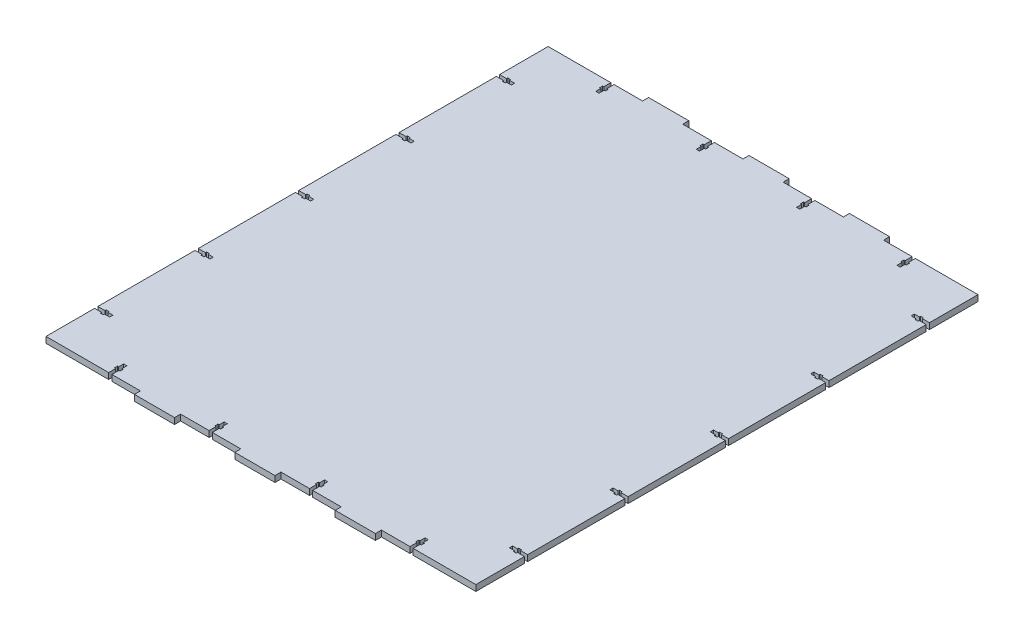
SolidWorks part; units mm, degrees
ref_plane "Front Plane" through (0, 0, 0) normal (0, 0, 1) x (1, 0, 0)
ref_plane "Top Plane" through (0, 0, 0) normal (0, 1, 0) x (1, 0, 0)
ref_plane "Right Plane" through (0, 0, 0) normal (1, 0, 0) x (0, 0, -1)
sketch "Sketch1" plane through (0, 0, 0) normal (0, 1, 0) x (1, 0, 0)
  line L1 (-214, -250) -> (214, -250)
  line L2 (-214, -250) -> (-214, 250)
  line L3 (-214, 250) -> (214, 250)
  line L4 (214, -250) -> (214, 250)
  line L5 (-214, -250) -> (214, 250) construction
  line L6 (-214, 250) -> (214, -250) construction
  point P0 (0, 0)
  dimension "D1" = 428
  dimension "D2" = 500
extrude "Boss-Extrude1" add sketch "Sketch1" along normal blind 6
sketch "Sketch2" plane through (0, 0, 0) normal (0, -1, 0) x (1, 0, 0)
  line L14 (0, 0) -> (0, 133.2527) construction
  line L15 (0, 0) -> (-145.1849, 0) construction
  line L40 (-148.4, 256) -> (-151.6, 256) construction
  line L41 (-148.4, 256) -> (-151.6, 256) construction
  line L42 (-48.4, 256) -> (-51.6, 256) construction
  line L43 (-48.4, 256) -> (-51.6, 256) construction
  line L44 (-148.4, 256) -> (-51.6, 256) construction
  line L45 (-214, 250) -> (214, 250) construction
  line L46 (-120, 256) -> (-80, 256)
  line L47 (-120, 256) -> (-120, 250)
  line L48 (-120, 250) -> (-80, 250)
  line L49 (-80, 256) -> (-80, 250)
  line L50 (-20, 250) -> (20, 250)
  line L51 (20, 256) -> (20, 250)
  line L52 (-20, 256) -> (20, 256)
  line L53 (-20, 256) -> (-20, 250)
  line L54 (80, 250) -> (120, 250)
  line L55 (120, 256) -> (120, 250)
  line L56 (80, 256) -> (120, 256)
  line L57 (80, 256) -> (80, 250)
  line L58 (120, -256) -> (120, -250)
  line L59 (80, -250) -> (120, -250)
  line L60 (80, -256) -> (120, -256)
  line L61 (80, -256) -> (80, -250)
  line L62 (20, -256) -> (20, -250)
  line L63 (-20, -256) -> (20, -256)
  line L64 (-20, -250) -> (20, -250)
  line L65 (-20, -256) -> (-20, -250)
  line L66 (-120, -250) -> (-80, -250)
  line L67 (-120, -256) -> (-120, -250)
  line L68 (-120, -256) -> (-80, -256)
  line L69 (-80, -256) -> (-80, -250)
  point P50 (-100, 256)
  dimension "D3" = 40
  dimension "D4" = 3
extrude "Boss-Extrude2" add sketch "Sketch2" against normal blind 6
sketch "Sketch3" plane through (0, 0, 0) normal (0, -1, 0) x (1, 0, 0)
  line L0 (-220, -198.4) -> (-220, -201.6) construction
  line L1 (-220, -198.4) -> (-220, -201.6)
  line L2 (-220, -200) -> (-193.4637, -200) construction
  line L3 (-214, -250) -> (-214, 250) construction
  line L4 (-199, -201.6) -> (-204, -201.6)
  line L5 (-199, -201.6) -> (-199, -198.4)
  line L6 (-199, -198.4) -> (-204, -198.4)
  line L7 (-214, -201.6) -> (-214, -198.4)
  line L8 (-199, -201.6) -> (-214, -198.4) construction
  line L9 (-199, -198.4) -> (-214, -201.6) construction
  line L10 (-207, -198.4) -> (-214, -198.4)
  line L11 (-204, -202.8) -> (-207, -202.8)
  line L12 (-204, -202.8) -> (-204, -201.6)
  line L13 (-204, -197.2) -> (-207, -197.2)
  line L14 (-207, -202.8) -> (-207, -201.6)
  line L15 (-204, -202.8) -> (-207, -197.2) construction
  line L16 (-204, -197.2) -> (-207, -202.8) construction
  line L17 (-207, -201.6) -> (-214, -201.6)
  line L18 (-199, -101.6) -> (-204, -101.6)
  line L19 (-207, -198.4) -> (-207, -197.2)
  line L20 (-204, -198.4) -> (-204, -197.2)
  line L21 (204, 202.8) -> (207, 197.2) construction
  line L22 (-199, -101.6) -> (-199, -98.4)
  line L24 (-199, -98.4) -> (-204, -98.4)
  line L25 (-214, -101.6) -> (-214, -98.4)
  line L26 (-207, -98.4) -> (-214, -98.4)
  line L27 (-204, -102.8) -> (-207, -102.8)
  line L28 (-204, -102.8) -> (-204, -101.6)
  line L29 (-204, -97.2) -> (-207, -97.2)
  line L30 (-207, -102.8) -> (-207, -101.6)
  line L31 (-207, -101.6) -> (-214, -101.6)
  line L32 (-207, -98.4) -> (-207, -97.2)
  line L33 (-204, -98.4) -> (-204, -97.2)
  line L34 (-199, -101.6) -> (-214, -98.4) construction
  line L35 (-199, -98.4) -> (-214, -101.6) construction
  line L36 (-204, -102.8) -> (-207, -97.2) construction
  line L37 (-204, -97.2) -> (-207, -102.8) construction
  line L38 (-199, -1.6) -> (-204, -1.6)
  line L39 (-199, -1.6) -> (-199, 1.6)
  line L40 (-199, 1.6) -> (-204, 1.6)
  line L41 (-214, -1.6) -> (-214, 1.6)
  line L42 (-207, 1.6) -> (-214, 1.6)
  line L43 (-204, -2.8) -> (-207, -2.8)
  line L44 (-204, -2.8) -> (-204, -1.6)
  line L45 (-204, 2.8) -> (-207, 2.8)
  line L46 (-207, -2.8) -> (-207, -1.6)
  line L47 (-207, -1.6) -> (-214, -1.6)
  line L48 (-207, 1.6) -> (-207, 2.8)
  line L49 (-204, 1.6) -> (-204, 2.8)
  line L50 (-199, -1.6) -> (-214, 1.6) construction
  line L51 (-199, 1.6) -> (-214, -1.6) construction
  line L52 (-204, -2.8) -> (-207, 2.8) construction
  line L53 (-204, 2.8) -> (-207, -2.8) construction
  line L54 (-199, 98.4) -> (-204, 98.4)
  line L55 (-199, 98.4) -> (-199, 101.6)
  line L56 (-199, 101.6) -> (-204, 101.6)
  line L57 (-214, 98.4) -> (-214, 101.6)
  line L58 (-207, 101.6) -> (-214, 101.6)
  line L59 (-204, 97.2) -> (-207, 97.2)
  line L60 (-204, 97.2) -> (-204, 98.4)
  line L61 (-204, 102.8) -> (-207, 102.8)
  line L62 (-207, 97.2) -> (-207, 98.4)
  line L63 (-207, 98.4) -> (-214, 98.4)
  line L64 (-207, 101.6) -> (-207, 102.8)
  line L65 (-204, 101.6) -> (-204, 102.8)
  line L66 (-199, 98.4) -> (-214, 101.6) construction
  line L67 (-199, 101.6) -> (-214, 98.4) construction
  line L68 (-204, 97.2) -> (-207, 102.8) construction
  line L69 (-204, 102.8) -> (-207, 97.2) construction
  line L70 (-199, 198.4) -> (-204, 198.4)
  line L71 (-199, 198.4) -> (-199, 201.6)
  line L72 (-199, 201.6) -> (-204, 201.6)
  line L73 (-214, 198.4) -> (-214, 201.6)
  line L74 (-207, 201.6) -> (-214, 201.6)
  line L75 (-204, 197.2) -> (-207, 197.2)
  line L76 (-204, 197.2) -> (-204, 198.4)
  line L77 (-204, 202.8) -> (-207, 202.8)
  line L78 (-207, 197.2) -> (-207, 198.4)
  line L79 (-207, 198.4) -> (-214, 198.4)
  line L80 (-207, 201.6) -> (-207, 202.8)
  line L81 (-204, 201.6) -> (-204, 202.8)
  line L82 (-199, 198.4) -> (-214, 201.6) construction
  line L83 (-199, 201.6) -> (-214, 198.4) construction
  line L84 (-204, 197.2) -> (-207, 202.8) construction
  line L85 (-204, 202.8) -> (-207, 197.2) construction
  line L86 (0, 0) -> (0, 128.8409) construction
  line L87 (204, 197.2) -> (207, 202.8) construction
  line L88 (199, 201.6) -> (214, 198.4) construction
  line L89 (199, 198.4) -> (214, 201.6) construction
  line L90 (204, 102.8) -> (207, 97.2) construction
  line L91 (204, 97.2) -> (207, 102.8) construction
  line L92 (199, 101.6) -> (214, 98.4) construction
  line L93 (199, 98.4) -> (214, 101.6) construction
  line L94 (204, 2.8) -> (207, -2.8) construction
  line L95 (204, -2.8) -> (207, 2.8) construction
  line L96 (199, 1.6) -> (214, -1.6) construction
  line L97 (199, -1.6) -> (214, 1.6) construction
  line L98 (204, -97.2) -> (207, -102.8) construction
  line L99 (204, -102.8) -> (207, -97.2) construction
  line L100 (199, -98.4) -> (214, -101.6) construction
  line L101 (199, -101.6) -> (214, -98.4) construction
  line L102 (204, -197.2) -> (207, -202.8) construction
  line L103 (204, -202.8) -> (207, -197.2) construction
  line L104 (199, -198.4) -> (214, -201.6) construction
  line L105 (199, -201.6) -> (214, -198.4) construction
  line L106 (204, 201.6) -> (204, 202.8)
  line L107 (207, 201.6) -> (207, 202.8)
  line L108 (207, 198.4) -> (214, 198.4)
  line L109 (207, 197.2) -> (207, 198.4)
  line L110 (204, 202.8) -> (207, 202.8)
  line L111 (204, 197.2) -> (204, 198.4)
  line L112 (204, 197.2) -> (207, 197.2)
  line L113 (207, 201.6) -> (214, 201.6)
  line L114 (214, 198.4) -> (214, 201.6)
  line L115 (199, 201.6) -> (204, 201.6)
  line L116 (199, 198.4) -> (199, 201.6)
  line L117 (199, 198.4) -> (204, 198.4)
  line L118 (204, 101.6) -> (204, 102.8)
  line L119 (207, 101.6) -> (207, 102.8)
  line L120 (207, 98.4) -> (214, 98.4)
  line L121 (207, 97.2) -> (207, 98.4)
  line L122 (204, 102.8) -> (207, 102.8)
  line L123 (204, 97.2) -> (204, 98.4)
  line L124 (204, 97.2) -> (207, 97.2)
  line L125 (207, 101.6) -> (214, 101.6)
  line L126 (214, 98.4) -> (214, 101.6)
  line L127 (199, 101.6) -> (204, 101.6)
  line L128 (199, 98.4) -> (199, 101.6)
  line L129 (199, 98.4) -> (204, 98.4)
  line L130 (204, 1.6) -> (204, 2.8)
  line L131 (207, 1.6) -> (207, 2.8)
  line L132 (207, -1.6) -> (214, -1.6)
  line L133 (207, -2.8) -> (207, -1.6)
  line L134 (204, 2.8) -> (207, 2.8)
  line L135 (204, -2.8) -> (204, -1.6)
  line L136 (204, -2.8) -> (207, -2.8)
  line L137 (207, 1.6) -> (214, 1.6)
  line L138 (214, -1.6) -> (214, 1.6)
  line L139 (199, 1.6) -> (204, 1.6)
  line L140 (199, -1.6) -> (199, 1.6)
  line L141 (199, -1.6) -> (204, -1.6)
  line L142 (204, -98.4) -> (204, -97.2)
  line L143 (207, -98.4) -> (207, -97.2)
  line L144 (207, -101.6) -> (214, -101.6)
  line L145 (207, -102.8) -> (207, -101.6)
  line L146 (204, -97.2) -> (207, -97.2)
  line L147 (204, -102.8) -> (204, -101.6)
  line L148 (204, -102.8) -> (207, -102.8)
  line L149 (207, -98.4) -> (214, -98.4)
  line L150 (214, -101.6) -> (214, -98.4)
  line L151 (199, -98.4) -> (204, -98.4)
  line L152 (199, -101.6) -> (199, -98.4)
  line L153 (204, -198.4) -> (204, -197.2)
  line L154 (207, -198.4) -> (207, -197.2)
  line L155 (199, -101.6) -> (204, -101.6)
  line L156 (207, -201.6) -> (214, -201.6)
  line L157 (207, -202.8) -> (207, -201.6)
  line L158 (204, -197.2) -> (207, -197.2)
  line L159 (204, -202.8) -> (204, -201.6)
  line L160 (204, -202.8) -> (207, -202.8)
  line L161 (207, -198.4) -> (214, -198.4)
  line L162 (214, -201.6) -> (214, -198.4)
  line L163 (199, -198.4) -> (204, -198.4)
  line L164 (199, -201.6) -> (199, -198.4)
  line L165 (199, -201.6) -> (204, -201.6)
  line L166 (-151.6, -256) -> (-148.4, -256) construction
  line L167 (-151.6, -256) -> (-148.4, -256) construction
  line L168 (-150, -256) -> (-150, -234.6121) construction
  line L169 (-120, -250) -> (-214, -250) construction
  line L170 (-151.6, -235) -> (-148.4, -235)
  line L171 (-151.6, -235) -> (-151.6, -240)
  line L172 (-151.6, -250) -> (-148.4, -250)
  line L173 (-148.4, -235) -> (-148.4, -240)
  line L174 (-151.6, -235) -> (-148.4, -250) construction
  line L175 (-151.6, -250) -> (-148.4, -235) construction
  line L176 (-148.4, -243) -> (-147.2, -243)
  line L177 (-152.8, -243) -> (-151.6, -243)
  line L178 (-152.8, -243) -> (-152.8, -240)
  line L179 (-152.8, -240) -> (-151.6, -240)
  line L180 (-147.2, -243) -> (-147.2, -240)
  line L181 (-152.8, -243) -> (-147.2, -240) construction
  line L182 (-152.8, -240) -> (-147.2, -243) construction
  line L183 (-151.6, -243) -> (-151.6, -250)
  line L184 (-148.4, -243) -> (-148.4, -250)
  line L185 (-148.4, -240) -> (-147.2, -240)
  line L186 (-51.6, -235) -> (-48.4, -235)
  line L187 (-51.6, -235) -> (-51.6, -240)
  line L188 (-51.6, -250) -> (-48.4, -250)
  line L189 (-48.4, -235) -> (-48.4, -240)
  line L190 (-48.4, -243) -> (-47.2, -243)
  line L191 (-52.8, -243) -> (-51.6, -243)
  line L192 (-52.8, -243) -> (-52.8, -240)
  line L193 (-52.8, -240) -> (-51.6, -240)
  line L194 (-47.2, -243) -> (-47.2, -240)
  line L195 (-51.6, -243) -> (-51.6, -250)
  line L196 (-48.4, -243) -> (-48.4, -250)
  line L197 (-48.4, -240) -> (-47.2, -240)
  line L198 (-51.6, -235) -> (-48.4, -250) construction
  line L199 (-51.6, -250) -> (-48.4, -235) construction
  line L200 (-52.8, -243) -> (-47.2, -240) construction
  line L201 (-52.8, -240) -> (-47.2, -243) construction
  line L202 (48.4, -235) -> (51.6, -235)
  line L203 (48.4, -235) -> (48.4, -240)
  line L204 (48.4, -250) -> (51.6, -250)
  line L205 (51.6, -235) -> (51.6, -240)
  line L206 (51.6, -243) -> (52.8, -243)
  line L207 (47.2, -243) -> (48.4, -243)
  line L208 (47.2, -243) -> (47.2, -240)
  line L209 (47.2, -240) -> (48.4, -240)
  line L210 (52.8, -243) -> (52.8, -240)
  line L211 (48.4, -243) -> (48.4, -250)
  line L212 (51.6, -243) -> (51.6, -250)
  line L213 (51.6, -240) -> (52.8, -240)
  line L214 (48.4, -235) -> (51.6, -250) construction
  line L215 (48.4, -250) -> (51.6, -235) construction
  line L216 (47.2, -243) -> (52.8, -240) construction
  line L217 (47.2, -240) -> (52.8, -243) construction
  line L218 (148.4, -235) -> (151.6, -235)
  line L219 (148.4, -235) -> (148.4, -240)
  line L220 (148.4, -250) -> (151.6, -250)
  line L221 (151.6, -235) -> (151.6, -240)
  line L222 (151.6, -243) -> (152.8, -243)
  line L223 (147.2, -243) -> (148.4, -243)
  line L224 (147.2, -243) -> (147.2, -240)
  line L225 (147.2, -240) -> (148.4, -240)
  line L226 (152.8, -243) -> (152.8, -240)
  line L227 (148.4, -243) -> (148.4, -250)
  line L228 (151.6, -243) -> (151.6, -250)
  line L229 (151.6, -240) -> (152.8, -240)
  line L230 (148.4, -235) -> (151.6, -250) construction
  line L231 (148.4, -250) -> (151.6, -235) construction
  line L232 (147.2, -243) -> (152.8, -240) construction
  line L233 (147.2, -240) -> (152.8, -243) construction
  line L234 (0, 0) -> (96.8105, 0) construction
  line L235 (147.2, 240) -> (152.8, 243) construction
  line L236 (147.2, 243) -> (152.8, 240) construction
  line L237 (148.4, 250) -> (151.6, 235) construction
  line L238 (148.4, 235) -> (151.6, 250) construction
  line L239 (47.2, 240) -> (52.8, 243) construction
  line L240 (47.2, 243) -> (52.8, 240) construction
  line L241 (48.4, 250) -> (51.6, 235) construction
  line L242 (48.4, 235) -> (51.6, 250) construction
  line L243 (-52.8, 240) -> (-47.2, 243) construction
  line L244 (-52.8, 243) -> (-47.2, 240) construction
  line L245 (-51.6, 250) -> (-48.4, 235) construction
  line L246 (-51.6, 235) -> (-48.4, 250) construction
  line L247 (-152.8, 240) -> (-147.2, 243) construction
  line L248 (-152.8, 243) -> (-147.2, 240) construction
  line L249 (-151.6, 250) -> (-148.4, 235) construction
  line L250 (-151.6, 235) -> (-148.4, 250) construction
  line L251 (151.6, 240) -> (152.8, 240)
  line L252 (151.6, 243) -> (151.6, 250)
  line L253 (148.4, 243) -> (148.4, 250)
  line L254 (152.8, 243) -> (152.8, 240)
  line L255 (147.2, 240) -> (148.4, 240)
  line L256 (147.2, 243) -> (147.2, 240)
  line L257 (147.2, 243) -> (148.4, 243)
  line L258 (151.6, 243) -> (152.8, 243)
  line L259 (151.6, 235) -> (151.6, 240)
  line L260 (148.4, 250) -> (151.6, 250)
  line L261 (148.4, 235) -> (148.4, 240)
  line L262 (148.4, 235) -> (151.6, 235)
  line L263 (51.6, 240) -> (52.8, 240)
  line L264 (51.6, 243) -> (51.6, 250)
  line L265 (48.4, 243) -> (48.4, 250)
  line L266 (52.8, 243) -> (52.8, 240)
  line L267 (47.2, 240) -> (48.4, 240)
  line L268 (47.2, 243) -> (47.2, 240)
  line L269 (47.2, 243) -> (48.4, 243)
  line L270 (51.6, 243) -> (52.8, 243)
  line L271 (51.6, 235) -> (51.6, 240)
  line L272 (48.4, 250) -> (51.6, 250)
  line L273 (48.4, 235) -> (48.4, 240)
  line L274 (48.4, 235) -> (51.6, 235)
  line L275 (-48.4, 240) -> (-47.2, 240)
  line L276 (-48.4, 243) -> (-48.4, 250)
  line L277 (-51.6, 243) -> (-51.6, 250)
  line L278 (-47.2, 243) -> (-47.2, 240)
  line L279 (-52.8, 240) -> (-51.6, 240)
  line L280 (-52.8, 243) -> (-52.8, 240)
  line L281 (-52.8, 243) -> (-51.6, 243)
  line L282 (-48.4, 243) -> (-47.2, 243)
  line L283 (-48.4, 235) -> (-48.4, 240)
  line L284 (-51.6, 250) -> (-48.4, 250)
  line L285 (-51.6, 235) -> (-51.6, 240)
  line L286 (-51.6, 235) -> (-48.4, 235)
  line L287 (-148.4, 240) -> (-147.2, 240)
  line L288 (-148.4, 243) -> (-148.4, 250)
  line L289 (-151.6, 243) -> (-151.6, 250)
  line L290 (-147.2, 243) -> (-147.2, 240)
  line L291 (-152.8, 240) -> (-151.6, 240)
  line L292 (-152.8, 243) -> (-152.8, 240)
  line L293 (-152.8, 243) -> (-151.6, 243)
  line L294 (-148.4, 243) -> (-147.2, 243)
  line L295 (-148.4, 235) -> (-148.4, 240)
  line L296 (-151.6, 250) -> (-148.4, 250)
  line L297 (-151.6, 235) -> (-151.6, 240)
  line L298 (-151.6, 235) -> (-148.4, 235)
  point P4 (-206.5, -200)
  point P11 (-205.5, -200)
  point P25 (-206.5, -100)
  point P31 (-205.5, -100)
  point P40 (-206.5, 0)
  point P45 (-205.5, 0)
  point P54 (-206.5, 100)
  point P59 (-205.5, 100)
  point P68 (-206.5, 200)
  point P73 (-205.5, 200)
  point P140 (205.5, 200)
  point P141 (206.5, 200)
  point P142 (205.5, 100)
  point P143 (206.5, 100)
  point P144 (205.5, 0)
  point P145 (206.5, 0)
  point P146 (205.5, -100)
  point P147 (206.5, -100)
  point P148 (205.5, -200)
  point P149 (206.5, -200)
  point P154 (-150, -242.5)
  point P161 (-150, -241.5)
  point P171 (-50, -242.5)
  point P176 (-50, -241.5)
  point P185 (50, -242.5)
  point P190 (50, -241.5)
  point P199 (150, -242.5)
  point P204 (150, -241.5)
  point P261 (150, 241.5)
  point P262 (150, 242.5)
  point P263 (50, 241.5)
  point P264 (50, 242.5)
  point P265 (-50, 241.5)
  point P266 (-50, 242.5)
  point P267 (-150, 241.5)
  point P268 (-150, 242.5)
  line M5 (214, -250) -> (214, 250)
  line M6 (214, 250) -> (120, 250)
  line M10 (80, 250) -> (20, 250)
  line M14 (-20, 250) -> (-80, 250)
  line M18 (-120, 250) -> (-214, 250)
  line M19 (-214, 250) -> (-214, -250)
  line M20 (-214, -250) -> (-120, -250)
  line M24 (-80, -250) -> (-20, -250)
  line M28 (20, -250) -> (80, -250)
  line M32 (120, -250) -> (214, -250)
  dimension "D1" = 15
  dimension "D2" = 3
  dimension "D3" = 7
  dimension "D4" = 5.6
  dimension "D5" = 5
  dimension "D6" = 15
  dimension "D7" = 5.6
  dimension "D8" = 7
  dimension "D9" = 4
extrude "Cut-Extrude1" cut sketch "Sketch3" against normal through all contours L297 L298 L295 L287 L290 L294 L288 L289 L293 L292 L291 M18 | L285 L286 L283 L275 L278 L282 L276 L277 L281 L280 L279 M14 | L261 L262 L259 L251 L254 L258 L252 L253 L257 L256 L255 M6 | L116 L117 L111 L112 L109 L108 L113 L107 L110 L106 L115 M5 | L128 L129 L123 L124 L121 L120 L125 L119 L122 L118 L127 M5 | L140 L141 L135 L136 L133 L132 L137 L131 L134 L130 L139 M5 | L152 L155 L147 L148 L145 L144 L149 L143 L146 L142 L151 M5 | L164 L165 L159 L160 L157 L156 L161 L154 L158 L153 L163 M5 | L229 L221 L218 L219 L225 L224 L223 L227 L228 L222 L226 M32 | L213 L205 L202 L203 L209 L208 L207 L211 L212 L206 L210 M28 | L197 L189 L186 L187 L193 L192 L191 L195 L196 L190 L194 M24 | L185 L173 L170 L171 L179 L178 L177 L183 L184 L176 L180 M20 | L6 L20 L13 L19 L10 L17 L14 L11 L12 L4 L5 M19 | L24 L33 L29 L32 L26 L31 L30 L27 L28 L18 L22 M19 | L72 L81 L77 L80 L74 L79 L78 L75 L76 L70 L71 M19 | L273 L274 L271 L263 L266 L270 L264 L265 L269 L268 L267 M10 | L40 L49 L45 L48 L42 L47 L46 L43 L44 L38 L39 M19 | L56 L65 L61 L64 L58 L57 L63 L62 L59 L60 L54 L55 region at (-150, 0, -242.3696) region at (-150, 0, 242.3696) region at (-206.3696, 0, 200) region at (-206.3696, 0, 0) region at (-206.3696, 0, -100) region at (-206.3696, 0, -200) region at (150, 0, 242.3696) region at (150, 0, -242.3696) region at (206.3696, 0, -200) region at (206.3696, 0, -100) region at (206.3696, 0, 0) region at (206.3696, 0, 100) region at (206.3696, 0, 200) region at (-50, 0, -242.3696) region at (50, 0, -242.3696) region at (50, 0, 242.3696) region at (-50, 0, 242.3696)
